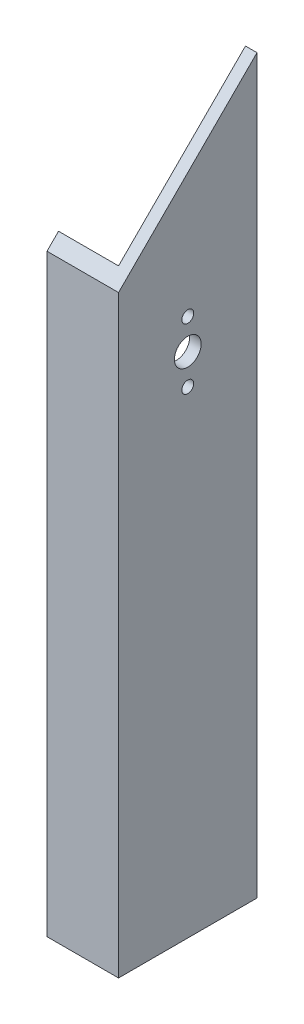
SolidWorks part; units mm, degrees
ref_plane "Front Plane" through (0, 0, 0) normal (0, 0, 1) x (1, 0, 0)
ref_plane "Top Plane" through (0, 0, 0) normal (0, 1, 0) x (1, 0, 0)
ref_plane "Right Plane" through (0, 0, 0) normal (1, 0, 0) x (0, 0, -1)
sketch "Sketch1" plane through (0, 0, 0) normal (0, 1, 0) x (1, 0, 0)
  line L0 (0, 0) -> (-19.685, 0)
  line L1 (-19.685, 0) -> (-19.685, 3.175)
  line L2 (-19.685, 3.175) -> (-3.175, 3.175)
  line L3 (-3.175, 3.175) -> (-3.175, 38.1)
  line L4 (-3.175, 38.1) -> (0, 38.1)
  line L5 (0, 38.1) -> (0, 0)
  dimension "D1" = 3.175
  dimension "D2" = 16.51
  dimension "D3" = 38.1
extrude "Boss-Extrude1" add sketch "Sketch1" along normal blind 203.2 contours L2 L3 L4 L5 L0 L1
sketch "Sketch2" plane through (0, 0, 0) normal (1, 0, 0) x (0, 0, -1)
  line L2 (38.1, 203.2) -> (0, 203.2) construction
  line L4 (0, 142.9065) -> (-14.0217, 144.6224)
  line L5 (-14.0217, 144.6224) -> (-5.0458, 217.9697)
  line L6 (-5.0458, 217.9697) -> (74.5137, 222.3899)
  line L7 (74.5137, 222.3899) -> (74.5137, 203.2)
  line L8 (0, 142.9065) -> (49.3603, 182.8469)
  line L9 (0, 203.2) -> (0, 0) construction
  line L10 (49.3603, 182.8469) -> (50.7689, 183.9867)
  line L11 (50.7689, 183.9867) -> (74.5137, 203.2)
sketch "Sketch5" plane through (-3.175, 0, 0) normal (-1, 0, 0) x (0, 0, 1)
  line L0 (0, 163.322) -> (-38.1, 201.422)
  line L1 (-38.1, 203.2) -> (-38.1, 0) construction
  line L2 (0, 203.2) -> (0, 0) construction
  line L3 (0, 163.322) -> (33.1966, 163.322)
  line L4 (33.1966, 163.322) -> (33.1966, 256.0472)
  line L5 (33.1966, 256.0472) -> (-60.8232, 256.0472)
  line L6 (-60.8232, 256.0472) -> (-60.8232, 201.422)
  line L7 (-60.8232, 201.422) -> (-38.1, 201.422)
  dimension "D1" = 163.322
  dimension "D2" = 135
extrude "Cut-Extrude3" cut sketch "Sketch5" against normal through all and the other way through all
ref_plane "Plane1" through (0, 0, -38.1) normal (0, 0, 1) x (1, 0, 0)
sketch "Sketch7" plane through (0, 0, 0) normal (1, 0, 0) x (0, 0, -1)
  line L0 (19.05, 131.318) -> (19.05, 148.082) construction
  line L1 (0, 139.7) -> (38.1, 139.7) construction
  line L2 (0, 163.322) -> (0, 0) construction
  line L3 (38.1, 201.422) -> (38.1, 0) construction
  line L4 (38.1, 0) -> (0, 0) construction
  circle A0 centre (19.05, 139.7) radius 3.683
  circle A1 centre (19.05, 148.082) radius 1.632
  circle A2 centre (19.05, 131.318) radius 1.632
  point P6 (19.05, 139.7)
  point P13 (19.05, 139.7)
  dimension "D1" = 7.366
  dimension "D3" = 3.2639
  dimension "D2" = 16.764
  dimension "D4" = 139.7
extrude "Cut-Extrude4" cut sketch "Sketch7" against normal through all
